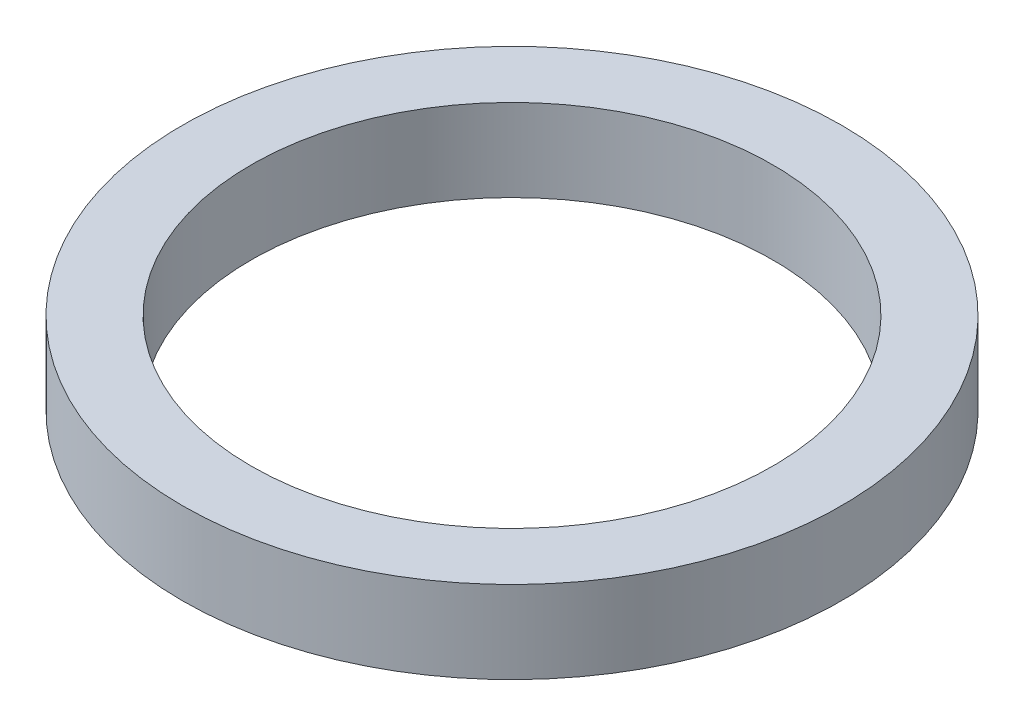
SolidWorks part; units mm, degrees
ref_plane "Front Plane" through (0, 0, 0) normal (0, 0, 1) x (1, 0, 0)
ref_plane "Top Plane" through (0, 0, 0) normal (0, 1, 0) x (1, 0, 0)
ref_plane "Right Plane" through (0, 0, 0) normal (1, 0, 0) x (0, 0, -1)
sketch "Sketch1" plane through (0, 0, 0) normal (0, 1, 0) x (1, 0, 0)
  circle A0 centre (0, 0) radius 60
  dimension "FLANGE_OD" = 120
extrude "Boss-Extrude1" add sketch "Sketch1" along normal blind 15
sketch "Sketch2" plane through (0, 0, 0) normal (0, 1, 0) x (1, 0, 0)
  circle A0 centre (0, 0) radius 47.5
  dimension "BORE_D" = 95
extrude "Cut-Extrude1" cut sketch "Sketch2" along normal through all
sketch "Sketch3" plane through (0, 15, 0) normal (0, 1, 0) x (1, 0, 0)
  circle A0 centre (0, 0) radius 27.6553 construction
  circle A1 centre (-27.6553, 0) radius 1.816
  dimension "BOLT_D" = 3.632
  dimension "BOLT_PCD" = 55.3107
extrude "Cut-Extrude2" cut sketch "Sketch3" against normal blind 10.7129 rebuild error yes
pattern_circular "CirPattern1" count 8 over 360 rebuild error yes
